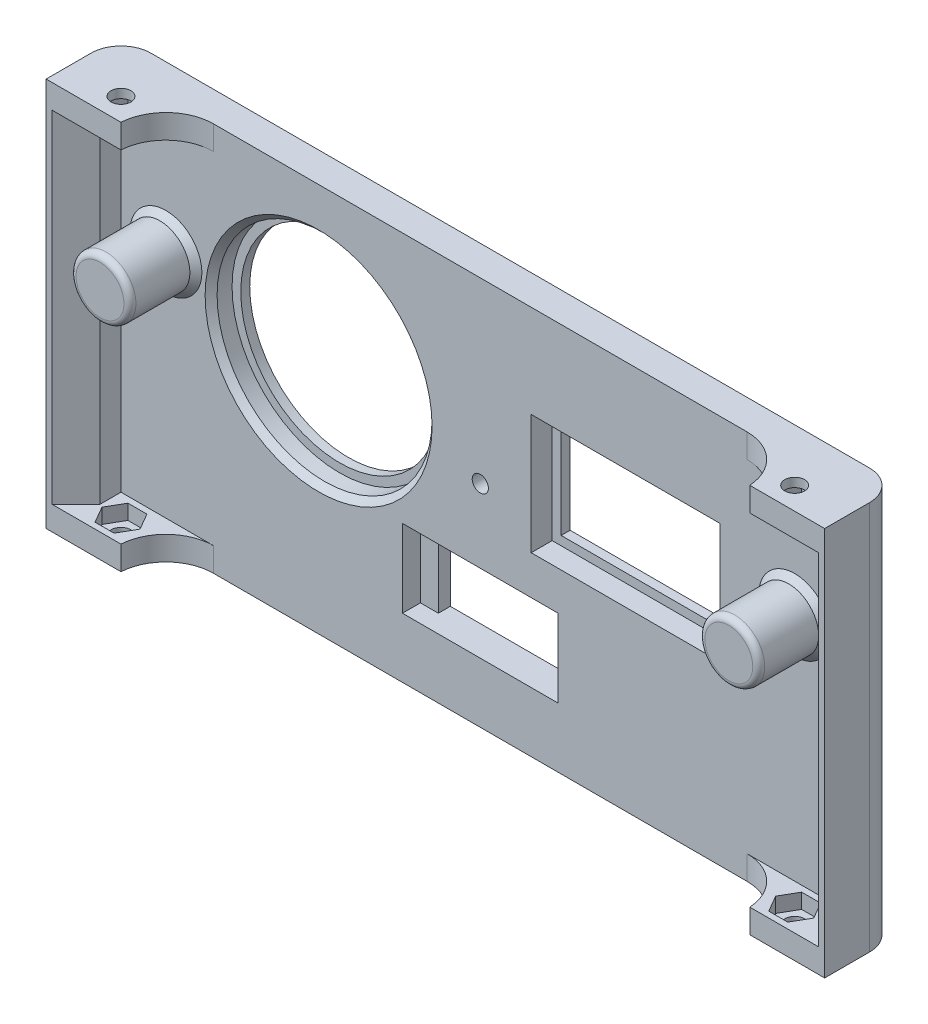
SolidWorks part; units mm, degrees
ref_plane "Front Plane" through (0, 0, 0) normal (0, 0, 1) x (1, 0, 0)
ref_plane "Top Plane" through (0, 0, 0) normal (0, 1, 0) x (1, 0, 0)
ref_plane "Right Plane" through (0, 0, 0) normal (1, 0, 0) x (0, 0, -1)
sketch "Sketch1" plane through (0, 0, 0) normal (0, 0, 1) x (1, 0, 0)
  line L1 (0, 0) -> (130, 0)
  line L2 (0, 0) -> (0, 65)
  line L3 (0, 65) -> (130, 65)
  line L4 (130, 0) -> (130, 65)
  dimension "D1" = 65
  dimension "D2" = 130
extrude "Boss-Extrude1" add sketch "Sketch1" along normal blind 12.5
sketch "Sketch3" plane through (0, 65, 0) normal (0, 1, 0) x (1, 0, 0)
  line L0 (5, -12.5) -> (125, -12.5)
  line L9 (125, -5) -> (125, -12.5)
  line L10 (5, -5) -> (125, -5)
  line L11 (5, -12.5) -> (5, -5)
  line L12 (125, -5) -> (125, -12.5)
  line L13 (5, -5) -> (125, -5)
  line L14 (5, -12.5) -> (5, -5)
  dimension "D1" = 5
extrude "Cut-Extrude1" cut sketch "Sketch3" against normal through all
fillet "Fillet1" radius 5 2 edges at (130, 32.5, 0) (0, 32.5, 0)
sketch "Sketch4" plane through (0, 0, 0) normal (0, -1, 0) x (1, 0, 0)
  line L0 (125, 5) -> (5, 5) construction
  line L1 (5, 12.5) -> (12.5, 12.5)
  line L2 (5, 12.5) -> (5, 5)
  line L3 (5, 5) -> (12.5, 5)
  line L4 (12.5, 12.5) -> (12.5, 5)
  line L6 (125, 5) -> (117.5, 5)
  line L7 (125, 5) -> (125, 12.5)
  line L8 (125, 12.5) -> (117.5, 12.5)
  line L9 (117.5, 5) -> (117.5, 12.5)
extrude "Boss-Extrude2" add sketch "Sketch4" against normal blind 4
sketch "Sketch5" plane through (0, 4, 0) normal (0, 1, 0) x (1, 0, 0)
  line L0 (121.25, -5) -> (121.25, -12.5) construction
  line L1 (117.5, -5) -> (125, -5) construction
  line L2 (125, -12.5) -> (117.5, -12.5) construction
  line L3 (65, 0) -> (65, -12.5) construction
  line L4 (124.4254, -8.75) -> (122.8377, -6)
  line L5 (122.8377, -6) -> (119.6623, -6)
  line L6 (119.6623, -6) -> (118.0746, -8.75)
  line L7 (118.0746, -8.75) -> (119.6623, -11.5)
  line L8 (119.6623, -11.5) -> (122.8377, -11.5)
  line L9 (122.8377, -11.5) -> (124.4254, -8.75)
  line L10 (125, 0) -> (5, 0) construction
  line L11 (10.3377, -6) -> (11.9254, -8.75)
  line L12 (11.9254, -8.75) -> (10.3377, -11.5)
  line L13 (7.1623, -11.5) -> (5.5746, -8.75)
  line L14 (10.3377, -11.5) -> (7.1623, -11.5)
  line L15 (7.1623, -6) -> (10.3377, -6)
  line L16 (5.5746, -8.75) -> (7.1623, -6)
  circle A0 centre (121.25, -8.75) radius 2.75 construction
  circle A1 centre (121.25, -8.75) radius 1.65
  circle A2 centre (8.75, -8.75) radius 1.65
  dimension "D2" = 3.3
  dimension "D1" = 5.5
extrude "Cut-Extrude2" cut sketch "Sketch5" against normal blind 2.5
extrude "Cut-Extrude3" cut sketch "Sketch5<3>" against normal through all contours A2 | A1 region at (121.25, 4, 8.75) region at (8.75, 4, 8.75)
sketch "Sketch5<3>" plane through (0, 4, 0) normal (0, 1, 0) x (1, 0, 0) same geometry as "Sketch5"
fillet "Fillet2" radius 8 2 edges at (117.5, 2, 5) (12.5, 2, 5)
ref_plane "Plane1" through (0, 32.5, 0) normal (0, 1, 0) x (1, 0, 0)
mirror "Mirror1" about plane through (0, 32.5, 0) normal (0, 1, 0) of "Cut-Extrude3", "Cut-Extrude2", "Boss-Extrude2", "Fillet2"
sketch "Sketch7" plane through (0, 0, 5) normal (0, 0, 1) x (1, 0, 0)
  line L0 (130, 0) -> (117.5, 0) construction
  line L1 (109.5156, 0) -> (20.4844, 0) construction
  line L2 (117.5, 0) -> (117.5, 42.5) construction
  line L3 (65, 65) -> (65, 0) construction
  line L4 (109.5156, 65) -> (20.4844, 65) construction
  circle A0 centre (117.5, 42.5) radius 5
  circle A1 centre (12.5, 42.5) radius 5
  dimension "D3" = 10
  dimension "D1" = 12.5
  dimension "D2" = 42.5
extrude "Boss-Extrude3" add sketch "Sketch7" along normal blind 11
fillet "Fillet3" radius 1 2 edges at (122.5, 42.5, 16) (7.5, 42.5, 16)
chamfer "Chamfer1" distance 1 angle 45 2 edges at (112.5, 42.5, 5) (7.5, 42.5, 5)
sketch "Sketch8" plane through (0, 0, 0) normal (0, 0, -1) x (-1, 0, 0)
  line L0 (-65, 65) -> (-65, 35.2375) construction
  line L1 (-125, 65) -> (-5, 65) construction
  circle A0 centre (-65, 35.2375) radius 1.35
  dimension "D2" = 2.7
  dimension "D1" = 29.7625
extrude "Cut-Extrude4" cut sketch "Sketch8" against normal through all
sketch "Sketch9" plane through (0, 0, 0) normal (0, 0, -1) x (-1, 0, 0)
  line L0 (-125, 32.5) -> (-5, 32.5) construction
  line L2 (-65, 65) -> (-65, 0) construction
  line L3 (-125, 65) -> (-5, 65) construction
  line L4 (-5, 0) -> (-125, 0) construction
  line L10 (-75, 23) -> (-55, 23)
  line L11 (-75, 23) -> (-75, 10)
  line L12 (-75, 10) -> (-55, 10)
  line L13 (-55, 23) -> (-55, 10)
  line L14 (-125, 65) -> (-125, 0) construction
  line L17 (-5, 0) -> (-5, 65) construction
  line L18 (-125, 39.5) -> (-5, 39.5) construction
  circle A0 centre (-38, 39.5) radius 16.5
  point P9 (-65, 23)
  point P21 (-35.0898, 42.5)
  point P22 (-34.9472, 39.5)
  dimension "D1" = 33
  dimension "D2" = 7
  dimension "D3" = 33
  dimension "D4" = 20
  dimension "D5" = 13
  dimension "D6" = 10
extrude "Cut-Extrude5" cut sketch "Sketch9" against normal blind 10 contours A0 region at (38, 39.5, 0)
sketch "Sketch10" plane through (0, 0, 5) normal (0, 0, 1) x (1, 0, 0)
  circle A0 centre (38, 39.5) radius 17.95
  dimension "D1" = 35.9
extrude "Cut-Extrude6" cut sketch "Sketch10" against normal offset from surface (3.5 mm away) 1.5 contours A0 up to face at (21.5, 39.5, 0)
chamfer "Chamfer3" distance 1 angle 45 1 edges at (55.95, 39.5, 5)
extrude "Cut-Extrude7" cut sketch "Sketch9<4>" against normal blind 10 contours L10 L13 L12 L11
sketch "Sketch9<4>" plane through (0, 0, 0) normal (0, 0, -1) x (-1, 0, 0) same geometry as "Sketch9"
sketch "Sketch11" plane through (0, 0, 5) normal (0, 0, 1) x (1, 0, 0)
  line L0 (125, 39.5) -> (5, 39.5) construction
  line L1 (73.5, 49.5) -> (105, 49.5)
  line L2 (73.5, 49.5) -> (73.5, 29.5)
  line L3 (73.5, 29.5) -> (105, 29.5)
  line L4 (105, 49.5) -> (105, 29.5)
  line L5 (75, 48) -> (103.5, 48)
  line L6 (103.5, 48) -> (103.5, 31)
  line L7 (75, 31) -> (103.5, 31)
  line L8 (75, 48) -> (75, 31)
  line L11 (125, 32.5) -> (5, 32.5) construction
  line L12 (125, 4) -> (125, 61) construction
  line L13 (6.875, 32.5) -> (-6.875, 32.5) construction
  line L14 (5, 4) -> (5, 61) construction
  point P14 (4.4566, 32.5)
  point P17 (105, 39.5)
  dimension "D1" = 31.5
  dimension "D2" = 20
  dimension "D4" = 20
  dimension "D3" = 1.5
  dimension "D5" = 7
extrude "Cut-Extrude8" cut sketch "Sketch11" against normal offset from surface (3.5 mm away) 1.5 up to face at (65, 16.5, 0)
sketch "Sketch13" plane through (0, 0, 5) normal (0, 0, 1) x (1, 0, 0)
  line L11 (75, 10) -> (55, 10) construction
  line L12 (55, 23) -> (52, 23)
  line L13 (55, 23) -> (55, 10)
  line L14 (55, 10) -> (52, 10)
  line L15 (52, 23) -> (52, 10)
  line L16 (75, 23) -> (78, 23)
  line L17 (75, 23) -> (75, 10)
  line L18 (75, 10) -> (78, 10)
  line L19 (78, 23) -> (78, 10)
  dimension "D1" = 3
extrude "Cut-Extrude10" cut sketch "Sketch13" against normal offset from surface (3 mm away) 2 up to face at (65, 16.5, 0)
extrude "Cut-Extrude11" cut sketch "Sketch11<2>" against normal blind 10 contours L5 L6 L7 L8
sketch "Sketch11<2>" plane through (0, 0, 5) normal (0, 0, 1) x (1, 0, 0) same geometry as "Sketch11"
chamfer "Chamfer4" distance 4 angle 45 2 edges at (5, 32.5, 12.5) (125, 32.5, 12.5)
